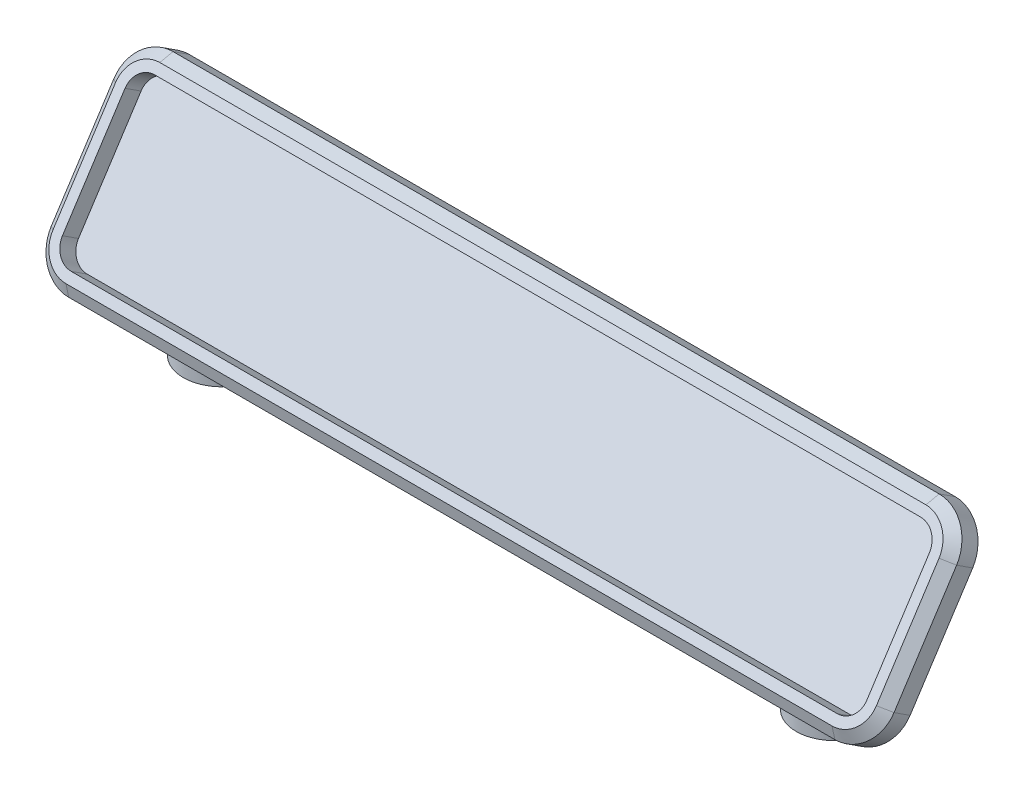
SolidWorks part; units mm, degrees
ref_plane "Front Plane" through (0, 0, 0) normal (0, 0, 1) x (1, 0, 0)
ref_plane "Top Plane" through (0, 0, 0) normal (0, 1, 0) x (1, 0, 0)
ref_plane "Right Plane" through (0, 0, 0) normal (1, 0, 0) x (0, 0, -1)
sketch "Sketch2" plane through (0, 0, 0) normal (0, 1, 0) x (1, 0, 0)
  line L0 (50.8, 0) -> (-50.8, 0) construction
  circle A0 centre (-50.8, 0) radius 6.35
  circle A1 centre (50.8, 0) radius 6.35
  point P8 (0, 0)
  dimension "D2" = 12.7
  dimension "D1" = 101.6
extrude "Boss-Extrude1" add sketch "Sketch2" along normal blind 19.05
ref_plane "Plane1" through (0, 19.05, 0) normal (0, 1, 0) x (1, 0, 0)
ref_axis "Axis1" through (88.99, 19.05, 0) along (-1, 0, 0)
ref_plane "Plane2" through (0, 5.6508, 8.7015) normal (0, 0.5446, 0.8387) x (-1, 0, 0)
sketch "Sketch3" plane through (0, 5.6508, 8.7015) normal (0, 0.5446, 0.8387) x (-1, 0, 0)
  line L0 (-50.8, -15.9767) -> (50.8, -15.9767)
  line L2 (-63.5, -31.8517) -> (63.5, -31.8517)
  line L3 (-69.85, -25.5017) -> (-69.85, -6.4517)
  line L4 (-63.5, -0.1017) -> (63.5, -0.1017)
  line L5 (69.85, -25.5017) -> (69.85, -6.4517)
  line L6 (-69.85, -31.8517) -> (69.85, -0.1017) construction
  line L7 (-69.85, -0.1017) -> (69.85, -31.8517) construction
  arc A0 (-63.5, -31.8517) -> (-69.85, -25.5017) centre (-63.5, -25.5017) cw
  arc A1 (63.5, -31.8517) -> (69.85, -25.5017) centre (63.5, -25.5017) ccw
  arc A2 (63.5, -0.1017) -> (69.85, -6.4517) centre (63.5, -6.4517) cw
  arc A3 (-69.85, -6.4517) -> (-63.5, -0.1017) centre (-63.5, -6.4517) cw
  ellipse E0 centre (50.8, -15.9767) end of major axis (44.45, -15.9767) minor radius 3.4585 construction
  ellipse E1 centre (-50.8, -15.9767) end of major axis (-57.15, -15.9767) minor radius 3.4585 construction
  ellipse E2 centre (50.8, -15.9767) end of major axis (44.45, -15.9767) minor radius 3.4585 construction
  ellipse E3 centre (-50.8, -15.9767) end of major axis (-57.15, -15.9767) minor radius 3.4585 construction
  point P22 (0, -15.9767)
  dimension "D3" = 6.35
  dimension "D1" = 139.7
  dimension "D2" = 31.75
extrude "Boss-Extrude2" add sketch "Sketch3" along normal blind 6.35 contours L2 L5 L4 L3 region at (66.9771, 29.9545, -7.0815)
sketch "Sketch8" plane through (0, 19.05, 0) normal (0, 1, 0) x (1, 0, 0)
  line L0 (44.45, 0) -> (57.15, 0) construction
  line L1 (-57.15, 0) -> (-44.45, 0) construction
  line L2 (44.45, 0) -> (57.15, 0)
  line L3 (-57.15, 0) -> (-44.45, 0)
  arc A0 (57.15, 0) -> (44.45, 0) centre (50.8, 0) ccw construction
  arc A1 (-44.45, 0) -> (-57.15, 0) centre (-50.8, 0) ccw construction
  arc A2 (57.15, 0) -> (44.45, 0) centre (50.8, 0) ccw
  arc A3 (-44.45, 0) -> (-57.15, 0) centre (-50.8, 0) ccw
  arc M1 (-44.45, 0) -> (-57.15, 0) centre (-50.8, 0) ccw
  line M2 (-57.15, 0) -> (-44.45, 0)
extrude "Boss-Extrude3" add sketch "Sketch8" along normal up to next contours L2 A2 | M2 M1 region at (50.8, 19.05, -2.695) region at (-50.8, 19.05, -2.695)
sketch "Sketch9" plane through (0, 9.1093, 14.0271) normal (0, 0.5446, 0.8387) x (1, 0, 0)
  line L8 (63.5, 28.6767) -> (-63.5, 28.6767)
  line L9 (-66.675, 25.5017) -> (-66.675, 6.4517)
  line L10 (-63.5, 3.2767) -> (63.5, 3.2767)
  line L11 (66.675, 6.4517) -> (66.675, 25.5017)
  line L12 (63.5, 28.6767) -> (-63.5, 28.6767)
  line L13 (-66.675, 25.5017) -> (-66.675, 6.4517)
  line L14 (-63.5, 3.2767) -> (63.5, 3.2767)
  line L15 (66.675, 6.4517) -> (66.675, 25.5017)
  arc A8 (63.5, 3.2767) -> (66.675, 6.4517) centre (63.5, 6.4517) ccw
  arc A9 (63.5, 3.2767) -> (66.675, 6.4517) centre (63.5, 6.4517) ccw
  arc A10 (66.675, 25.5017) -> (63.5, 28.6767) centre (63.5, 25.5017) ccw
  arc A11 (66.675, 25.5017) -> (63.5, 28.6767) centre (63.5, 25.5017) ccw
  arc A12 (-63.5, 28.6767) -> (-66.675, 25.5017) centre (-63.5, 25.5017) ccw
  arc A13 (-63.5, 28.6767) -> (-66.675, 25.5017) centre (-63.5, 25.5017) ccw
  arc A14 (-66.675, 6.4517) -> (-63.5, 3.2767) centre (-63.5, 6.4517) ccw
  arc A15 (-66.675, 6.4517) -> (-63.5, 3.2767) centre (-63.5, 6.4517) ccw
  point P1 (62.9944, 3.0767)
  point P2 (-63.5, 28.8767)
  point P3 (66.875, 25.0121)
  point P4 (66.875, 7.045)
  point P7 (-63.0018, 3.0767)
  point P9 (63.9758, 28.8767)
  point P12 (-63.0018, 28.8767)
  point P13 (-66.875, 25.0121)
  point P14 (-66.875, 6.9695)
  dimension "D1" = 3.175
extrude "Cut-Extrude1" cut sketch "Sketch9" against normal blind 3.175
chamfer "Chamfer2" distance 1.5875 angle 45 16 edges at (-69.85, 19.05, 0) (0, 32.3639, -8.6461) (69.85, 19.05, 0) (0, 5.7361, 8.6461) (0, 9.1946, 13.9717) (-69.85, 22.5085, 5.3256) (69.85, 22.5085, 5.3256) (0, 35.8224, -3.3206) (67.9901, 30.8041, -7.6332) (-67.9901, 30.8041, -7.6332) (67.9901, 7.2959, 7.6332) (-67.9901, 7.2959, 7.6332) (67.9901, 10.7544, 12.9587) (-67.9901, 10.7544, 12.9587) (67.9901, 34.2625, -2.3076) (-67.9901, 34.2625, -2.3076)
hole_wizard "Hole1" positions "3DSketch1" profile "Sketch10" legacy
sketch3d "3DSketch1"
  line L0 (-50.8, 28.8281, 0) -> (-50.8, 0, 0) construction
  line L1 (50.8, 28.8281, 0) -> (50.8, 0, 0) construction
  point P0 (-50.8, 0, 0)
  point P4 (50.8, 0, 0)
sketch "Sketch10" plane through (-50.8, 0, 0) normal (1, 0, 0) x (0, 0, -1)
  line L0 (0, 0) -> (0, 10.16)
  line L1 (0, 10.16) -> (2.54, 10.16)
  line L2 (2.54, 10.16) -> (2.54, 0.6858)
  line L3 (2.54, 0.6858) -> (3.175, 0.6858)
  line L4 (3.175, 0.6858) -> (3.175, 0)
  line L5 (3.175, 0) -> (0, 0)
  line L6 (0, 110) -> (0, -10) construction
  dimension "Diameter" = 5.08
  dimension "Depth" = 10.16
  dimension "C-Bore Diameter" = 6.35
  dimension "C-Bore Depth" = 0.6858
